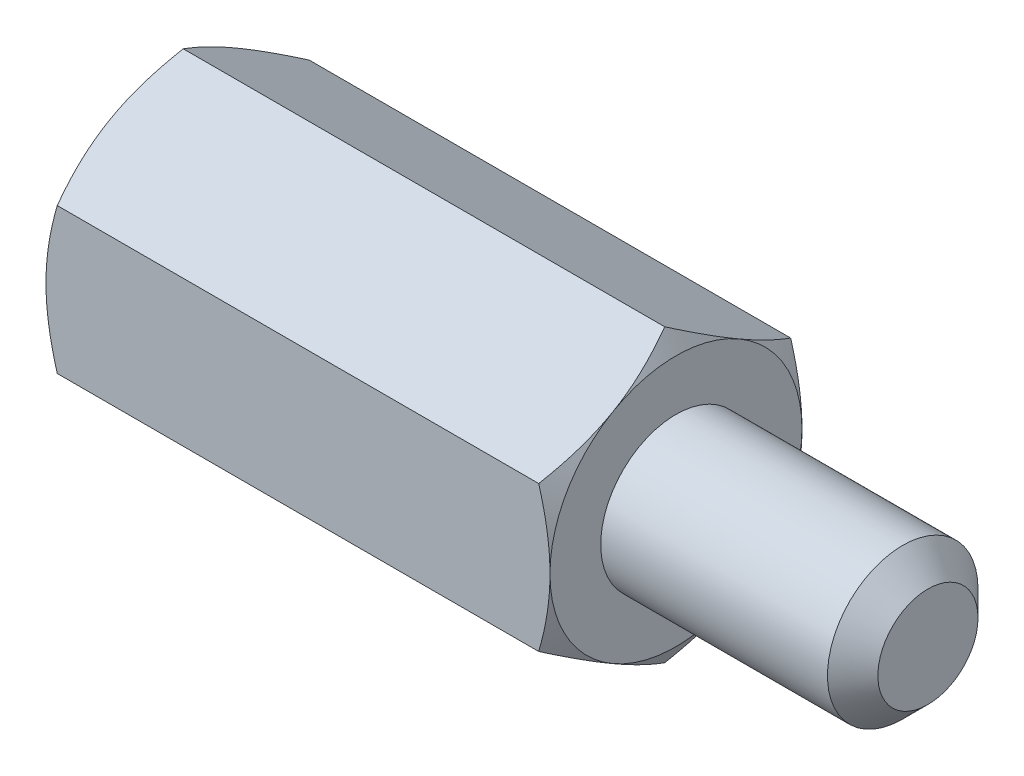
SolidWorks part; units mm, degrees
ref_plane "Front Plane" through (0, 0, 0) normal (0, 0, 1) x (1, 0, 0)
ref_plane "Top Plane" through (0, 0, 0) normal (0, 1, 0) x (1, 0, 0)
ref_plane "Right Plane" through (0, 0, 0) normal (1, 0, 0) x (0, 0, -1)
sketch "Sketch1" plane through (0, 0, 0) normal (0, 0, 1) x (1, 0, 0)
  line L0 (-7.1438, 0) -> (7.1437, 0) construction
  line L1 (7.1438, 1.4224) -> (7.1438, -1.4224) construction
  line L2 (-7.1438, 2.3813) -> (-7.1438, -2.3813) construction
  line L3 (-0.7938, 1.4224) -> (-0.7938, -1.4224) construction
  line L4 (-0.7938, -1.4224) -> (-7.1437, -1.4224) construction
  line L5 (-0.7938, 1.4224) -> (-7.1437, 1.4224) construction
  line L6 (-7.1438, 2.3813) -> (2.3812, 2.3813) construction
  line L7 (-7.1438, -2.3813) -> (2.3812, -2.3813) construction
  point P2 (2.3812, 0)
  point P8 (-0.7938, 0)
  point P13 (4.2863, -1.4224)
  dimension "D1" = 2.8575
  dimension "Hex" = 4.7625
  dimension "Male Thread" = 2.8448
  dimension "A" = 9.525
  dimension "B" = 4.7625
  dimension "C" = 6.35
  dimension "Female Thread" = 2.8448
ref_plane "Plane1" through (7.1437, 0, 0) normal (1, 0, 0) x (0, 0, -1)
sketch "Sketch2" plane through (7.1437, 0, 0) normal (1, 0, 0) x (0, 0, -1)
  circle A0 centre (0, 0) radius 1.4224
extrude "Extrude1" add sketch "Sketch2" against normal up to vertex (4.7625 mm away) up to point (2.3812, 0, 0)
sketch "Sketch3" plane through (7.1437, 0, 0) normal (1, 0, 0) x (0, 0, -1)
  circle A1 centre (0, 0) radius 1.4224
  circle A2 centre (0, 0) radius 1.4224
  dimension "D1" = 0
curve "Helix/Spiral1" pitch 0.635 height 5.3975 turns 8.5 parameters "Male Pitch"=0.635
chamfer "Chamfer1" distance 0.4763 angle 45 1 edges at (7.1437, 0, -1.4224)
sketch "Sketch4" plane through (0, 0, 0) normal (0, 0, 1) x (1, 0, 0)
  line L0 (7.1438, 1.4224) -> (7.6994, 1.4224)
  line L1 (7.6994, 1.4224) -> (7.4612, 1.01)
  line L2 (7.4612, 1.01) -> (7.3819, 1.01)
  line L3 (7.3819, 1.01) -> (7.1438, 1.4224)
  line L4 (7.4216, 1.01) -> (7.4216, 1.4224) construction
  line L5 (7.2628, 1.2162) -> (7.5803, 1.2162) construction
  dimension "D1" = 0.0794
  dimension "D2" = 0.3175
  dimension "D3" = 60
sweep "Cut-Sweep1" [suppressed] cut profiles "Sketch4" path "Helix/Spiral1"
sketch "Sketch16" [suppressed] plane through (0, 0, 0) normal (0, 0, 1) x (1, 0, 0)
  line L0 (2.3813, 1.0074) -> (3.4925, 1.0074)
  line L1 (3.4925, 1.0074) -> (3.9075, 1.4224)
  line L2 (3.9075, 1.4224) -> (2.3813, 1.4224)
  line L3 (2.3813, 1.4224) -> (2.3813, 1.0074)
  line L4 (7.1438, 1.4224) -> (7.6994, 1.4224) construction
  line L5 (0, 0) -> (7.1437, 0) construction
  line L6 (7.1437, -0.9462) -> (7.1437, 0.9462) construction
  dimension "D1" = 1.1113
  dimension "D2" = 45
  dimension "D3" = 0.0025
revolve "Cut-Revolve1" [suppressed] cut sketch "Sketch16" angle 360 about L5
ref_plane "Plane2" through (2.3812, 0, 0) normal (1, 0, 0) x (0, 0, -1)
sketch "Sketch7" plane through (2.3812, 0, 0) normal (1, 0, 0) x (0, 0, -1)
  line L1 (0, 2.7496) -> (-2.3813, 1.3748)
  line L2 (-2.3813, 1.3748) -> (-2.3812, -1.3748)
  line L3 (-2.3812, -1.3748) -> (0, -2.7496)
  line L4 (0, -2.7496) -> (2.3812, -1.3748)
  line L5 (2.3812, -1.3748) -> (2.3812, 1.3748)
  line L6 (2.3812, 1.3748) -> (0, 2.7496)
  circle A0 centre (0, 0) radius 2.3813 construction
extrude "Extrude4" add sketch "Sketch7" against normal up to vertex (9.525 mm away) up to point (-7.1438, 0, 0)
sketch "Sketch17" plane through (0, 0, 0) normal (0, 0, 1) x (1, 0, 0)
  line L0 (-7.1438, -2.7496) -> (2.3812, -2.7496) construction
  line L1 (-7.1438, 2.7496) -> (2.3812, 2.7496) construction
  line L2 (-7.1438, -2.7496) -> (2.3812, -2.7496)
  line L3 (-7.1438, 2.7496) -> (2.3812, 2.7496)
sketch "Sketch8" plane through (-7.1438, 0, 0) normal (-1, 0, 0) x (0, 0, 1)
  circle A0 centre (0, 0) radius 2.3813 construction
  circle A1 centre (0, 0) radius 2.3813
extrude "Extrude5" cut sketch "Sketch8" against normal through all draft 60 flip side to cut
sketch "Sketch9" plane through (2.3812, 0, 0) normal (1, 0, 0) x (0, 0, -1)
  circle A0 centre (0, 0) radius 2.3813 construction
  circle A1 centre (0, 0) radius 2.3813
extrude "Extrude6" cut sketch "Sketch9" against normal through all draft 60 flip side to cut
sketch "Sketch10" plane through (-7.1438, 0, 0) normal (-1, 0, 0) x (0, 0, 1)
  line L0 (0, 0) -> (-1.0058, 1.0058) construction
  line L1 (0, 0) -> (-1.4224, 0) construction
  circle A0 centre (0, 0) radius 1.4224
  dimension "D1" = 45
extrude "Extrude7" cut sketch "Sketch10" against normal up to vertex (6.35 mm away) up to point (-0.7938, 0, 0)
sketch "Sketch11" plane through (-7.1438, 0, 0) normal (-1, 0, 0) x (0, 0, 1)
  circle A0 centre (0, 0) radius 1.4224 construction
  circle A1 centre (0, 0) radius 1.4224
curve "Helix/Spiral2" pitch 0.635 height 6.35 turns 10 parameters "Female Pitch"=0.635
sketch "Sketch12" plane through (0, 0, 0) normal (0, 0, 1) x (1, 0, 0)
  line L0 (-7.6994, 1.4224) -> (-7.4612, 1.01)
  line L1 (-7.4612, 1.01) -> (-7.3819, 1.01)
  line L2 (-7.3819, 1.01) -> (-7.1437, 1.4224)
  line L3 (-7.6994, 1.4224) -> (-7.1437, 1.4224)
  line L4 (-7.4216, 1.01) -> (-7.4216, 1.4224) construction
  line L5 (-7.1438, 2.3813) -> (-7.1438, -2.3813) construction
  line L6 (-7.5803, 1.2162) -> (-7.2628, 1.2162) construction
  dimension "D1" = 60
  dimension "D2" = 0.0794
  dimension "D3" = 0.3175
sweep "Sweep3" [suppressed] add profiles "Sketch12" path "Helix/Spiral2"
sketch "Sketch13" plane through (-7.1438, 0, 0) normal (-1, 0, 0) x (0, 0, 1)
  circle A2 centre (0, 0) radius 1.4732
  circle A3 centre (0, 0) radius 1.4732
  dimension "D1" = 0.0508
extrude "Extrude8" [suppressed] cut sketch "Sketch13" along normal through all and the other way through all draft 45
equation "\"D3@Helix/Spiral1\" = \"B@Sketch1\"+\"Male Pitch@Helix/Spiral1\"*1"
equation "\"D1@Chamfer1\" = \"Male Pitch@Helix/Spiral1\"*.750"
equation "\"D1@Sketch4\" = \"Male Pitch@Helix/Spiral1\"*.125"
equation "\"D2@Sketch4\" = \"Male Pitch@Helix/Spiral1\"*.5"
equation "\"D2@Sketch12\" = \"Male Pitch@Helix/Spiral1\"*.125"
equation "\"D3@Sketch12\" = \"Male Pitch@Helix/Spiral1\"*.5"
equation "\"D3@Helix/Spiral2\" = \"C@Sketch1\""
equation "\"Female Thread@Sketch1\" = \"Male Thread@Sketch1\""
equation "\"Female Pitch@Helix/Spiral2\" = \"Male Pitch@Helix/Spiral1\""
equation "\"D1@Sketch16\" = \"Male Pitch@Helix/Spiral1\"*1.75"
equation "\"D1@Sketch1\" = \"Male Pitch@Helix/Spiral1\"*4.5"
